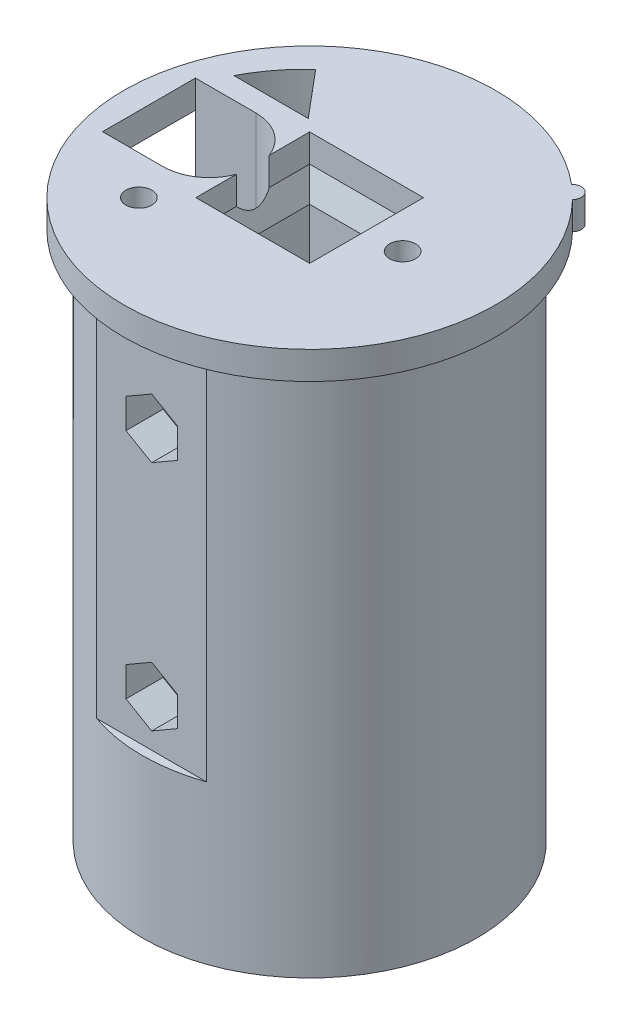
SolidWorks part; units mm, degrees
ref_plane "Спереди" through (0, 0, 0) normal (0, 0, 1) x (1, 0, 0)
ref_plane "Сверху" through (0, 0, 0) normal (0, 1, 0) x (1, 0, 0)
ref_plane "Справа" through (0, 0, 0) normal (1, 0, 0) x (0, 0, -1)
sketch "Sketch1" plane through (0, 0, 0) normal (0, 1, 0) x (1, 0, 0)
  line L0 (-5.125, 0) -> (-18, 0) construction
  line L1 (5.125, -5.125) -> (-5.125, -5.125)
  line L2 (5.125, -5.125) -> (5.125, 5.125)
  line L3 (5.125, 5.125) -> (-5.125, 5.125)
  line L4 (-5.125, -5.125) -> (-5.125, 5.125)
  line L5 (5.125, -5.125) -> (-5.125, 5.125) construction
  line L6 (5.125, 5.125) -> (-5.125, -5.125) construction
  circle A0 centre (0, 0) radius 18
  circle A1 centre (-12, 0) radius 2
  dimension "D1" = 36
  dimension "D3" = 6
  dimension "D2" = 10.25
extrude "Boss-Extrude1" add sketch "Sketch1" along normal blind 57
sketch "Sketch2" plane through (0, 57, 0) normal (0, 1, 0) x (1, 0, 0)
  line L0 (-10.8, 5) -> (-17.2916, 5)
  line L1 (-10.8, -5) -> (-17.2916, -5)
  line L2 (-5.125, 0) -> (-18, 0) construction
  line L3 (-5.125, 5.125) -> (-5.125, -5.125) construction
  circle A1 centre (0, 0) radius 18 construction
  arc A2 (-17.2916, 5) -> (-17.2916, -5) centre (0, 0) ccw
  arc A3 (-10.8, 5) -> (-10.8, -5) centre (-10.8, 0) cw
  point P12 (-5.8, 0)
  dimension "D1" = 5
extrude "Cut-Extrude1" cut sketch "Sketch2" against normal blind 7
sketch "Sketch4" plane through (0, 0, 0) normal (0, -1, 0) x (-1, 0, 0)
  line L0 (0, 0) -> (18, 21.4516) construction
  line L1 (0, 0) -> (18, -21.4516) construction
  line L2 (18, 21.4516) -> (18, -21.4516) construction
  line L3 (0, 0) -> (13.6996, 11.6756) construction
  line L4 (0, 0) -> (13.6996, -11.6756) construction
  line L5 (0, 0) -> (18, 0) construction
  line L6 (5.125, 5.125) -> (5.125, -5.125) construction
  line L7 (11.5702, 13.7888) -> (5.1423, 6.1284) construction
  line L8 (5.1423, 6.1284) -> (5.1423, -4.3826) construction
  line L9 (5.1423, -4.3826) -> (13.6996, -11.6756) construction
  line L10 (5.1423, 0.8729) -> (18.1354, 0.8729) construction
  line L12 (15.8104, 5.5479) -> (6.4604, 5.5479)
  line L13 (15.8104, 5.5479) -> (15.8104, -3.8021)
  line L14 (15.8104, -3.8021) -> (6.4604, -3.8021)
  line L15 (6.4604, 5.5479) -> (6.4604, -3.8021)
  line L16 (15.8104, 5.5479) -> (6.4604, -3.8021) construction
  line L17 (15.8104, -3.8021) -> (6.4604, 5.5479) construction
  arc A0 (13.6996, -11.6756) -> (11.5702, 13.7888) centre (0.5154, 0.0431) ccw construction
  circle A2 centre (0, 0) radius 18 construction
  point P2 (11, 0)
  point P5 (11.5702, 13.7888)
  point P7 (4.1157, 3.5076)
  point P8 (11.5702, -13.7888)
  point P11 (5.125, -6.1077)
  point P16 (11.1354, 0.8729)
  dimension "D5" = 10
  dimension "D1" = 100
  dimension "D2" = 3
  dimension "D3" = 3
  dimension "D4" = 9.35
  dimension "D6" = 7
extrude "Cut-Extrude3" cut sketch "Sketch4" against normal blind 20.4
sketch "Sketch5" plane through (0, 57, 0) normal (0, 1, 0) x (1, 0, 0)
  line L0 (0, 18) -> (0, -18) construction
  line L1 (5.9161, 17) -> (-5.9161, 17)
  line L2 (5.9161, -17) -> (-5.9161, -17)
  circle A0 centre (0, 0) radius 18 construction
  arc A1 (5.9161, 17) -> (-5.9161, 17) centre (0, 0) ccw
  arc A2 (5.9161, -17) -> (-5.9161, -17) centre (0, 0) cw
  point P11 (0, 17)
  dimension "D1" = 1
extrude "Cut-Extrude4" cut sketch "Sketch5" against normal blind 40
sketch "Sketch6" plane through (0, 0, -17) normal (0, 0, -1) x (-1, 0, 0)
  line L0 (0, 57) -> (0, 0) construction
  line L1 (5.9161, 57) -> (-5.9161, 57) construction
  line L2 (5.9161, 17) -> (-5.9161, 17) construction
  line L3 (5.9161, 0) -> (-5.9161, 0) construction
  circle A0 centre (0, 47) radius 1.5
  circle A1 centre (0, 22) radius 1.5
  point P2 (0, 24.4843)
  dimension "D1" = 3
  dimension "D2" = 10
  dimension "D3" = 5
extrude "Cut-Extrude5" cut sketch "Sketch6" against normal through all
sketch "Sketch7" plane through (0, 0, -17) normal (0, 0, -1) x (-1, 0, 0)
  circle A0 centre (0, 47) radius 3
  circle A1 centre (0, 22) radius 3
  dimension "D1" = 6
extrude "Cut-Extrude6" cut sketch "Sketch7" against normal blind 3
sketch "Sketch8" plane through (0, 0, 17) normal (0, 0, 1) x (1, 0, 0)
  line L0 (5.9161, 17) -> (5.9161, 57) construction
  line L1 (0, 43.8) -> (2.7713, 45.4)
  line L2 (2.7713, 45.4) -> (2.7713, 48.6)
  line L3 (2.7713, 48.6) -> (0, 50.2)
  line L4 (0, 50.2) -> (-2.7713, 48.6)
  line L5 (-2.7713, 48.6) -> (-2.7713, 45.4)
  line L6 (-2.7713, 45.4) -> (0, 43.8)
  line L9 (0, 18.8) -> (2.7713, 20.4)
  line L10 (2.7713, 20.4) -> (2.7713, 23.6)
  line L11 (2.7713, 23.6) -> (0, 25.2)
  line L12 (0, 25.2) -> (-2.7713, 23.6)
  line L13 (-2.7713, 23.6) -> (-2.7713, 20.4)
  line L14 (-2.7713, 20.4) -> (0, 18.8)
  circle A0 centre (0, 47) radius 3.2 construction
  circle A1 centre (0, 22) radius 3.2 construction
  dimension "D1" = 6.4
extrude "Cut-Extrude7" cut sketch "Sketch8" against normal blind 4
chamfer "Chamfer1" distance 1 angle 70 4 edges at (-5.125, 57, 0) (0, 57, -5.125) (0, 57, 5.125) (5.125, 57, 0) first distance on face at (-5.2523, 57, 0)
sketch "Sketch9" plane through (0, 0, 0) normal (0, -1, 0) x (1, 0, 0)
  line L0 (16.4542, -7.2979) -> (-16.4542, -7.2979) construction
  line L1 (-15.8104, -5.5479) -> (-6.4604, -5.5479) construction
  line L2 (-7.4542, -7.2979) -> (-15.4542, -7.2979)
  line L3 (-7.4542, -7.2979) -> (-11.6323, -12.2772)
  line L4 (5.125, -5.125) -> (-5.125, -5.125) construction
  circle A0 centre (0, 0) radius 18 construction
  arc A1 (-15.4542, -7.2979) -> (-11.6323, -12.2772) centre (0.5168, 1.0043) ccw
  point P10 (-11.4542, -7.2979)
  dimension "D8" = 18
  dimension "D1" = 1.75
  dimension "D2" = 5
  dimension "D3" = 6.5
  dimension "D4" = 50
  dimension "D5" = 8
  dimension "D6" = 2.1729
  dimension "D7" = 23.9084
extrude "Cut-Extrude8" cut sketch "Sketch9" against normal through all
sketch "Sketch12" plane through (0, 57, 0) normal (0, 1, 0) x (1, 0, 0)
  line L0 (18, 0) -> (-10.8, 0) construction
  line L1 (0, 0) -> (-12.7279, -12.7279) construction
  arc A0 (5.9161, -17) -> (5.9161, 17) centre (0, 0) ccw construction
  arc A1 (-17.2916, -5) -> (-5.9161, -17) centre (0, 0) ccw construction
  circle A2 centre (10, 0) radius 1.4
  circle A3 centre (-9.1924, -9.1924) radius 1.4
  dimension "D1" = 2.8
  dimension "D2" = 10
  dimension "D3" = 13
extrude "Cut-Extrude10" cut sketch "Sketch12" against normal blind 20
sketch "Sketch13" plane through (0, 57, 0) normal (0, 1, 0) x (1, 0, 0)
  line L0 (-10.8, 5) -> (-17.2916, 5)
  line L1 (-6.125, 6.125) -> (6.125, 6.125)
  line L2 (-7.4542, 7.2979) -> (-15.4542, 7.2979)
  line L3 (-6.125, -6.125) -> (6.125, -6.125)
  line L4 (6.125, 6.125) -> (6.125, -6.125)
  line L5 (-6.125, 6.125) -> (6.125, -6.125) construction
  line L6 (-6.125, -6.125) -> (6.125, 6.125) construction
  line L7 (-17.2916, -5) -> (-10.8, -5)
  line L8 (-17.2916, 5) -> (-17.2916, -5)
  line L9 (-6.125, 1.7732) -> (-6.125, 6.125)
  line L10 (-6.125, -1.7732) -> (-6.125, -6.125)
  line L11 (-7.4542, 7.2979) -> (-11.6323, 12.2772)
  circle A0 centre (0, 0) radius 20
  arc A1 (-10.8, 5) -> (-6.125, 1.7732) centre (-10.8, 0) cw
  arc A2 (-6.125, -1.7732) -> (-10.8, -5) centre (-10.8, 0) cw
  circle A3 centre (10, 0) radius 1.4
  circle A4 centre (-9.1924, -9.1924) radius 1.4
  arc A5 (-11.6323, 12.2772) -> (-15.4542, 7.2979) centre (0.5168, -1.0043) ccw
  dimension "D1" = 40
extrude "Boss-Extrude2" add sketch "Sketch13" along normal blind 3
sketch "Sketch14" plane through (0, 60, 0) normal (0, 1, 0) x (1, 0, 0)
  line L0 (0, 0) -> (0, 20) construction
  line L1 (0, 0) -> (12.8558, 15.3209) construction
  line L2 (12.8558, 15.3209) -> (14.3216, 13.9603)
  circle A0 centre (0, 0) radius 20 construction
  arc A1 (12.8558, 15.3209) -> (14.3216, 13.9603) centre (13.5887, 14.6406) cw
  dimension "D2" = 1
  dimension "D1" = 40
  dimension "D3" = 2
extrude "Boss-Extrude3" add sketch "Sketch14" against normal up to surface (3 mm away) up to face at (0, 57, 20)
